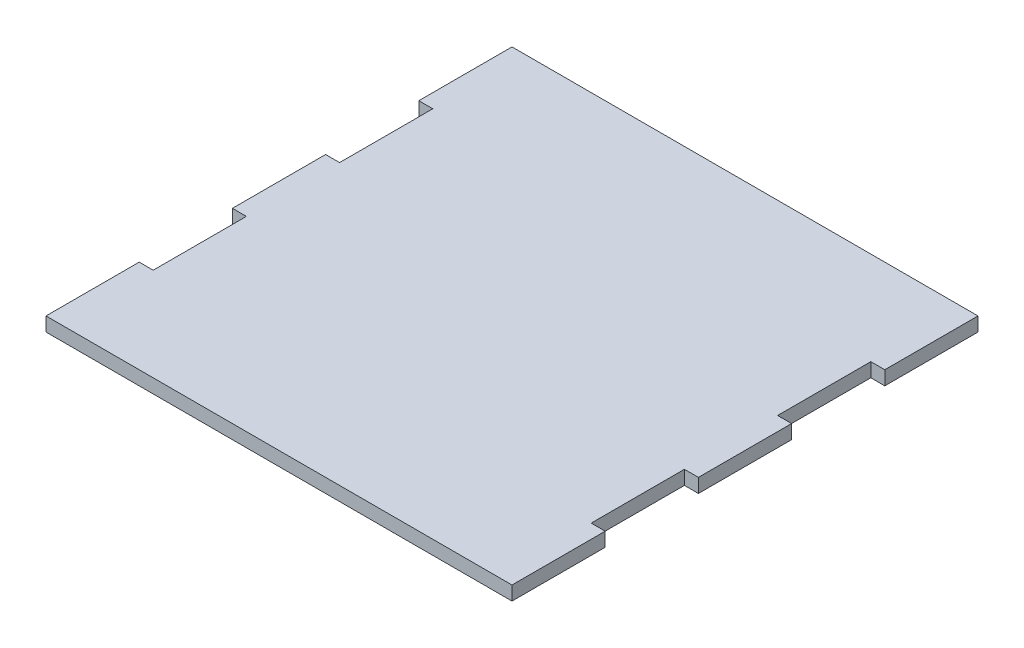
SolidWorks part; units mm, degrees
material "Pine"
ref_plane "Front Plane" through (0, 0, 0) normal (0, 0, 1) x (1, 0, 0)
ref_plane "Top Plane" through (0, 0, 0) normal (0, 1, 0) x (1, 0, 0)
ref_plane "Right Plane" through (0, 0, 0) normal (1, 0, 0) x (0, 0, -1)
sketch "Sketch1" plane through (0, 0, 0) normal (0, 1, 0) x (1, 0, 0)
  line L1 (-100, 100) -> (100, 100)
  line L2 (-100, 100) -> (-100, -100)
  line L3 (-100, -100) -> (100, -100)
  line L4 (100, 100) -> (100, -100)
  line L5 (-100, 100) -> (100, -100) construction
  line L6 (-100, -100) -> (100, 100) construction
  point P0 (0, 0)
  dimension "D1" = 200
  dimension "D2" = 200
extrude "Boss-Extrude1" add sketch "Sketch1" along normal blind 6
sketch "Sketch2" plane through (0, 6, 0) normal (0, 1, 0) x (1, 0, 0)
  line L0 (-100, 100) -> (-100, -100) construction
  line L1 (-100, 60) -> (-94, 60)
  line L2 (-100, 60) -> (-100, 20)
  line L3 (-100, 20) -> (-94, 20)
  line L4 (-94, 60) -> (-94, 20)
  line L5 (100, 100) -> (-100, 100) construction
  line L6 (94, 60) -> (94, 20)
  line L7 (94, 60) -> (100, 60)
  line L8 (100, 60) -> (100, 20)
  line L9 (94, 20) -> (100, 20)
  line L10 (94, -20) -> (94, -60)
  line L11 (94, -20) -> (100, -20)
  line L12 (100, -20) -> (100, -60)
  line L13 (94, -60) -> (100, -60)
  line L14 (-100, -20) -> (-100, -60)
  line L15 (-100, -20) -> (-94, -20)
  line L16 (-94, -20) -> (-94, -60)
  line L17 (-100, -60) -> (-94, -60)
  dimension "D1" = 40
  dimension "D2" = 40
  dimension "D3" = 6
  dimension "D4" = 2
  dimension "D5" = 2
extrude "Cut-Extrude1" cut sketch "Sketch2" against normal blind 6
